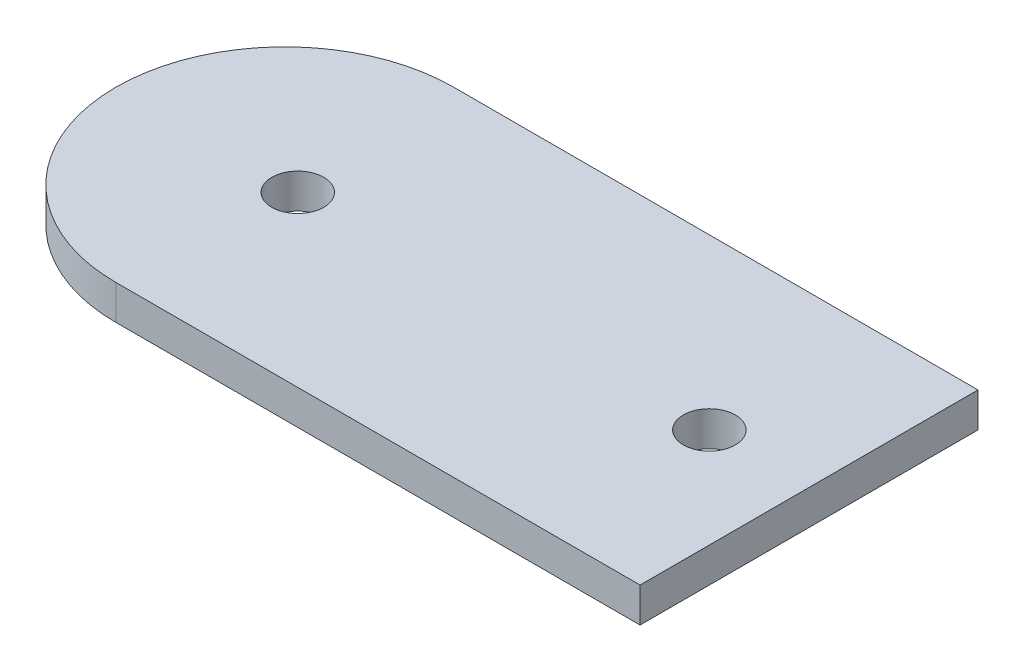
SolidWorks part; units mm, degrees
ref_plane "Front Plane" through (0, 0, 0) normal (0, 0, 1) x (1, 0, 0)
ref_plane "Top Plane" through (0, 0, 0) normal (0, 1, 0) x (1, 0, 0)
ref_plane "Right Plane" through (0, 0, 0) normal (1, 0, 0) x (0, 0, -1)
sketch "Sketch1" plane through (0, 0, 0) normal (0, 1, 0) x (1, 0, 0)
  line L0 (20, 0) -> (14.25, 0)
  line L1 (-20, -9.75) -> (20, -9.75)
  line L2 (-20, -9.75) -> (-20, 9.75)
  line L3 (-20, 9.75) -> (20, 9.75)
  line L4 (20, -9.75) -> (20, 9.75)
  line L5 (-20, -9.75) -> (20, 9.75) construction
  line L6 (-20, 9.75) -> (20, -9.75) construction
  line L7 (14.25, 0) -> (-9.5, 0)
  circle A0 centre (-9.5, 0) radius 1.5
  circle A1 centre (14.25, 0) radius 1.5
  point P0 (0, 0)
  dimension "D1" = 40
  dimension "D2" = 19.5
  dimension "D3" = 5.75
  dimension "D4" = 23.75
extrude "Boss-Extrude1" add sketch "Sketch1" along normal blind 2 contours A1 L4 L3 L2 L1 A0 region at (19.555, 0, 4.875)
fillet "Fillet1" radius 9.75 2 edges at (-20, 1, -9.75) (-20, 1, 9.75)
